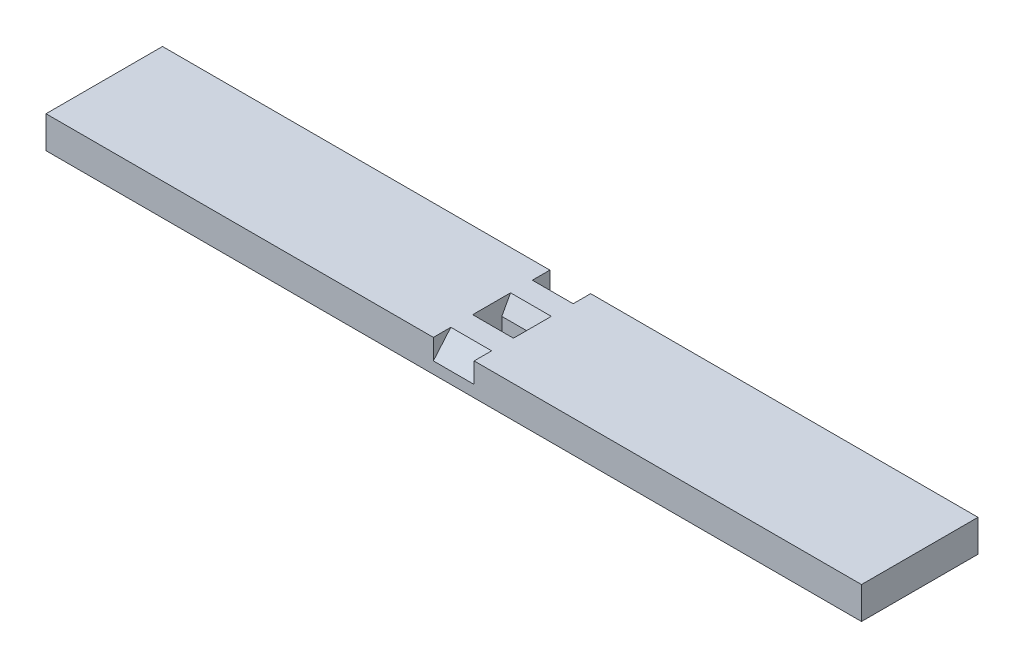
SolidWorks part; units mm, degrees
ref_plane "Front Plane" through (0, 0, 0) normal (0, 0, 1) x (1, 0, 0)
ref_plane "Top Plane" through (0, 0, 0) normal (0, 1, 0) x (1, 0, 0)
ref_plane "Right Plane" through (0, 0, 0) normal (1, 0, 0) x (0, 0, -1)
sketch "Sketch1" plane through (0, 0, 0) normal (0, 1, 0) x (1, 0, 0)
  line L1 (0, 0) -> (140, 0)
  line L2 (0, 0) -> (0, 20)
  line L3 (0, 20) -> (140, 20)
  line L4 (140, 0) -> (140, 20)
  dimension "D1" = 20
  dimension "D2" = 140
extrude "Boss-Extrude1" add sketch "Sketch1" along normal blind 5.5
sketch "Sketch2" plane through (0, 5.5, 0) normal (0, 1, 0) x (1, 0, 0)
  line L0 (70, 20) -> (70, 0) construction
  line L1 (140, 20) -> (0, 20) construction
  line L2 (0, 0) -> (140, 0) construction
  line L4 (66.5, 8.25) -> (73.5, 8.25)
  line L5 (66.5, 8.25) -> (66.5, 11.75)
  line L6 (66.5, 11.75) -> (73.5, 11.75)
  line L7 (73.5, 8.25) -> (73.5, 11.75)
  line L8 (66.5, 8.25) -> (73.5, 11.75) construction
  line L9 (66.5, 11.75) -> (73.5, 8.25) construction
  point P6 (70, 10)
  dimension "D1" = 3.5
  dimension "D2" = 7
extrude "Cut-Extrude1" cut sketch "Sketch2" against normal blind 10
sketch "Sketch3" plane through (66.5, 0, 0) normal (1, 0, 0) x (0, 0, -1)
  line L0 (8.25, 5.5) -> (6.7479, 5.5)
  line L1 (20, 5.5) -> (0, 5.5) construction
  line L2 (6.7479, 5.5) -> (8.25, 2.75)
  line L3 (8.25, 0) -> (8.25, 5.5) construction
  line L4 (8.25, 2.75) -> (8.25, 5.5)
  line L5 (11.75, 5.5) -> (13.25, 5.5)
  line L6 (13.25, 5.5) -> (11.75, 2.75)
  line L7 (11.75, 0) -> (11.75, 5.5) construction
  line L8 (11.75, 2.75) -> (11.75, 5.5)
  line L9 (3, 5.5) -> (0, 2)
  line L11 (0, 2) -> (0, 5.5)
  line L12 (0, 5.5) -> (3, 5.5)
  line L13 (17, 5.5) -> (20, 2)
  line L15 (20, 2) -> (20, 5.5)
  line L16 (20, 5.5) -> (17, 5.5)
  dimension "D1" = 1.5021
  dimension "D2" = 1.5
  dimension "D3" = 3
  dimension "D4" = 3
  dimension "D5" = 3.5
  dimension "D6" = 3.5
extrude "Cut-Extrude2" cut sketch "Sketch3" along normal up to surface (7 mm away) up to face at (73.5, 2.75, -10)
